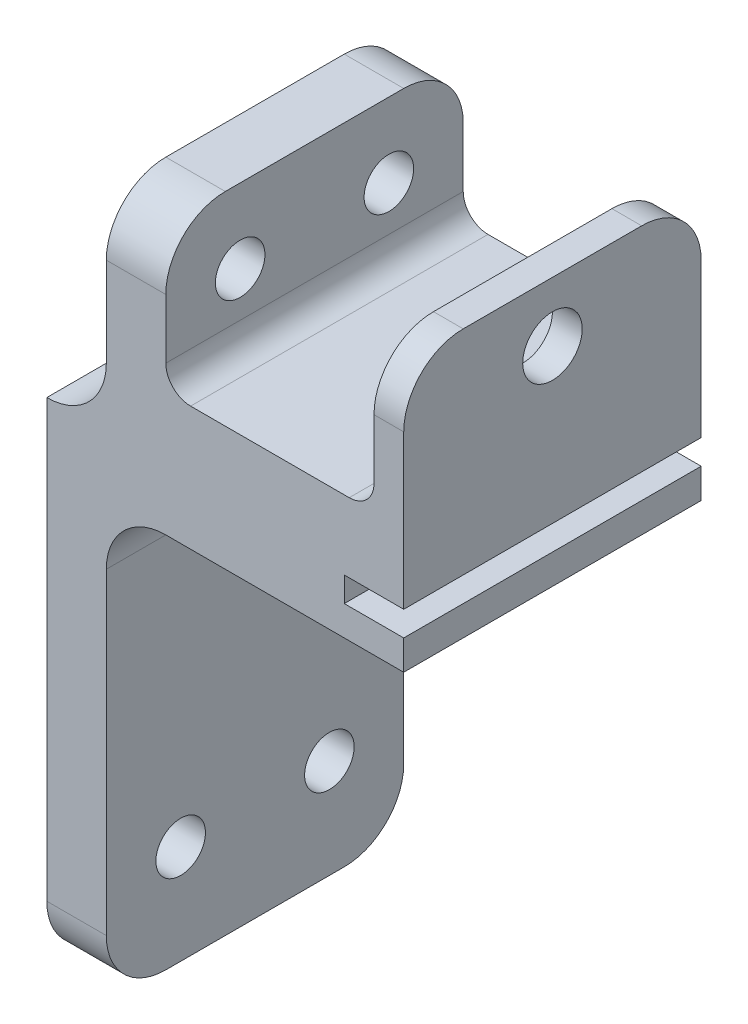
SolidWorks part; units mm, degrees
ref_plane "Front Plane" through (0, 0, 0) normal (0, 0, 1) x (1, 0, 0)
ref_plane "Top Plane" through (0, 0, 0) normal (0, 1, 0) x (1, 0, 0)
ref_plane "Right Plane" through (0, 0, 0) normal (1, 0, 0) x (0, 0, -1)
sketch "Sketch2" plane through (0, 0, 0) normal (0, 0, 1) x (1, 0, 0)
  line L0 (0, -12) -> (0, -88)
  line L1 (0, -88) -> (-12, -88)
  line L2 (-12, -88) -> (-12, 12)
  line L3 (-12, 12) -> (0, 12)
  line L4 (0, 12) -> (0, 54)
  line L5 (0, 54) -> (12, 54)
  line L6 (12, 54) -> (12, 30)
  line L7 (17, 25) -> (49, 25)
  line L8 (54, 30) -> (54, 54)
  line L9 (54, 54) -> (60, 54)
  line L10 (60, 54) -> (60, 11)
  line L16 (60, 11) -> (48, 11)
  line L17 (48, 11) -> (48, 6)
  line L18 (48, 6) -> (60, 6)
  line L19 (60, 6) -> (60, 0)
  line L20 (60, 0) -> (12, 0)
  arc A0 (0, -12) -> (12, 0) centre (12, -12) cw
  arc A1 (49, 25) -> (54, 30) centre (49, 30) ccw
  arc A2 (12, 30) -> (17, 25) centre (17, 30) ccw
  point P19 (57.8074, 8.8397)
  point P20 (0, 0)
  dimension "D14" = 12
  dimension "D15" = 5
  dimension "D1" = 100
  dimension "D2" = 142
  dimension "D3" = 12
  dimension "D4" = 6
  dimension "D5" = 42
  dimension "D6" = 25
  dimension "D7" = 12
  dimension "D8" = 72
  dimension "D9" = 11
  dimension "D10" = 5
  dimension "D11" = 142
  dimension "D12" = 12
  dimension "D13" = 43
extrude "Boss-Extrude1" add sketch "Sketch2" along normal blind 60
fillet "Fillet1" radius 12 1 edges at (0, 12, 30)
fillet "Fillet2" radius 12 6 edges at (-6, -88, 0) (-6, -88, 60) (57, 54, 0) (57, 54, 60) (6, 54, 0) (6, 54, 60)
sketch "Sketch4" plane through (-12, 0, 0) normal (-1, 0, 0) x (0, 0, 1)
  line L0 (48, -88) -> (12, -88) construction
  line L1 (60, 12) -> (60, -76) construction
  line L2 (48, 54) -> (12, 54) construction
  line L3 (60, 42) -> (60, 24) construction
  circle A0 centre (15, -68) radius 5
  circle A1 centre (45, -68) radius 5
  circle A2 centre (15, 39) radius 5
  circle A3 centre (45, 39) radius 5
  point P8 (0, 0)
  point P9 (0, 0)
  dimension "D1" = 10
  dimension "D2" = 30
  dimension "D3" = 20
  dimension "D4" = 15
  dimension "D5" = 30
  dimension "D6" = 15
  dimension "D7" = 15
extrude "Cut-Extrude1" cut sketch "Sketch4" against normal up to next
sketch "Sketch5" plane through (60, 0, 0) normal (1, 0, 0) x (0, 0, -1)
  line L0 (0, 11) -> (0, 42) construction
  line L1 (-48, 54) -> (-12, 54) construction
  circle A0 centre (-30, 42) radius 6
  point P6 (-28.594, 30.4542)
  dimension "D1" = 12
  dimension "D2" = 30
  dimension "D3" = 12
extrude "Cut-Extrude2" cut sketch "Sketch5" against normal up to next
